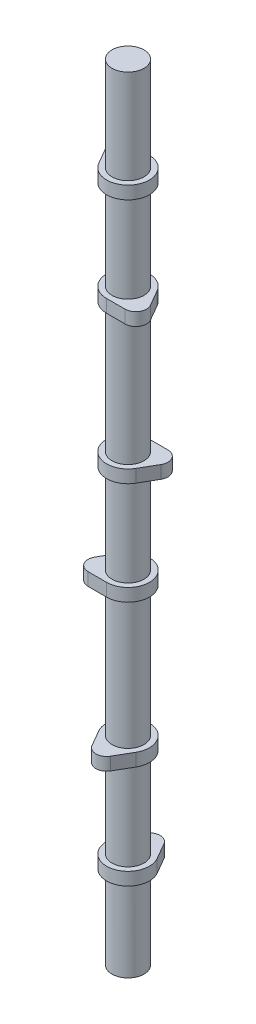
SolidWorks part; units mm, degrees
ref_plane "Front Plane" through (0, 0, 0) normal (0, 0, 1) x (1, 0, 0)
ref_plane "Top Plane" through (0, 0, 0) normal (0, 1, 0) x (1, 0, 0)
ref_plane "Right Plane" through (0, 0, 0) normal (1, 0, 0) x (0, 0, -1)
sketch "Sketch1" plane through (0, 0, 0) normal (0, 1, 0) x (1, 0, 0)
  line L0 (-10.9985, 6.35) -> (-5.4993, 15.875)
  line L1 (5.4993, 15.875) -> (10.9985, 6.35)
  arc A0 (-10.9985, 6.35) -> (10.9985, 6.35) centre (0, 0) ccw
  arc A1 (5.4993, 15.875) -> (-5.4993, 15.875) centre (0, 12.7) ccw
  dimension "D1" = 25.4
  dimension "D2" = 12.7
  dimension "D3" = 12.7
extrude "Boss-Extrude1" add sketch "Sketch1" along normal mid plane 7.62
ref_axis "Axis1" through (0, 129.6956, 0) along (0, -1, 0)
move or copy body "Body-Move/Copy1" bodies to move or copy 101 copy yes number of copies 1 translate (0, 60.96, 0) parameters "D1"=0, "D2"=0, "D3"=0
move or copy body "Body-Move/Copy2" bodies to move or copy 102 copy no rotation origin (0, 0, 0) rotation axis (0, 1, 0) rotation angle 180
sketch "Sketch2" plane through (0, 0, 0) normal (0, 1, 0) x (1, 0, 0)
  circle A0 centre (0, 0) radius 9.5
  dimension "D1" = 19
extrude "Boss-Extrude2" add sketch "Sketch2" along normal blind 146.05 from offset 25.4 offset against normal yes
pattern_linear "LPattern1" count 3 spacing 146.05 along (0, 1, 0) of bodies 104
move or copy body "Body-Move/Copy3" bodies to move or copy 105 copy no rotation origin (0, 0, 0) rotation axis (0, 1, 0) rotation angle 120
move or copy body "Body-Move/Copy4" bodies to move or copy 106 copy no rotation origin (0, 0, 0) rotation axis (0, -1, 0) rotation angle 120
sketch "Sketch3" plane through (0, 412.75, 0) normal (0, 1, 0) x (1, 0, 0)
  circle A1 centre (0, 0) radius 9.5
  circle A2 centre (0, 0) radius 9.5
  dimension "D1" = 0
sketch "Sketch4" plane through (0, -25.4, 0) normal (0, -1, 0) x (1, 0, 0)
  circle A1 centre (0, 0) radius 9.5
  circle A2 centre (0, 0) radius 9.5
  dimension "D1" = 0
extrude "Boss-Extrude3" add sketch "Sketch4" along normal blind 27.94
combine bodies "Combine1" operation type add bodies to combine 108 107 109
